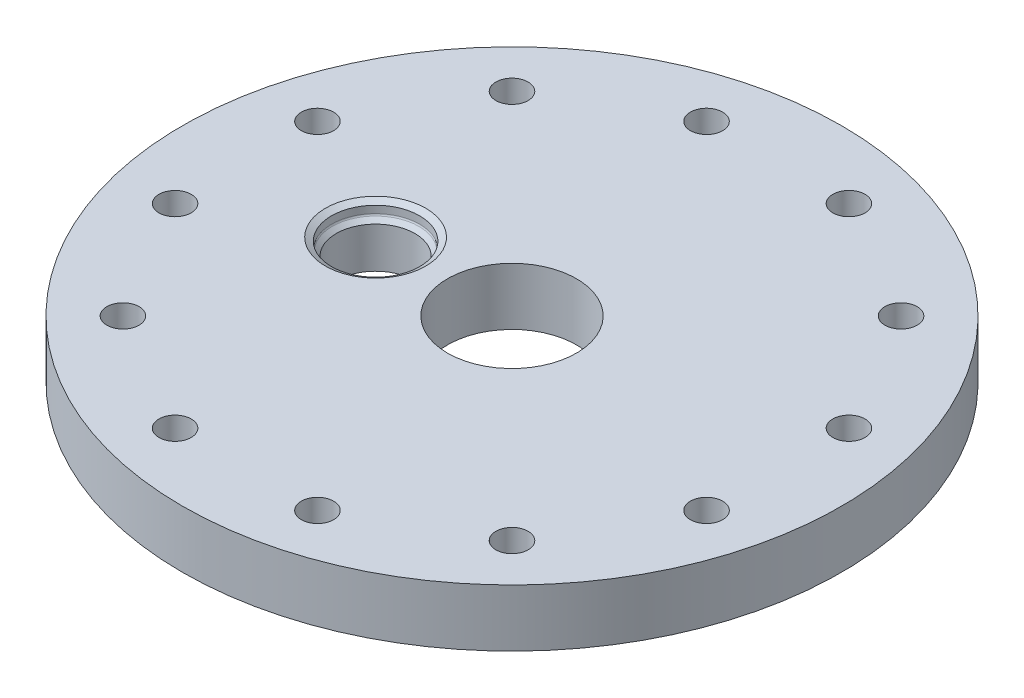
SolidWorks part; units mm, degrees
note: '?' marks a value the reader was unsure of.
material "7075-T6, Plate (SS)"
ref_plane "Front Plane" through (0, 0, 0) normal (0, 0, 1) x (1, 0, 0)
ref_plane "Top Plane" through (0, 0, 0) normal (0, 1, 0) x (1, 0, 0)
ref_plane "Right Plane" through (0, 0, 0) normal (1, 0, 0) x (0, 0, -1)
sketch "Top Plate Diameter" plane through (0, 0, 0) normal (0, 1, 0) x (1, 0, 0)
  circle A0 centre (0, 0) radius 73.025
  dimension "D1" = 146.05
extrude "Top Plate Extrude" add sketch "Top Plate Diameter" along normal blind 12.7
ref_axis "Center of Top Plate" through (0, 12.7, 0) along (0, -1, 0)?
sketch "Fuel Port Clearance Diameter" plane through (0, 12.7, 0) normal (0, 1, 0) x (1, 0, 0)
  circle A0 centre (0, 0) radius 14.2875
  dimension "D1" = 28.575
extrude "Fuel Port Clearance Hole" cut sketch "Fuel Port Clearance Diameter" against normal through all
hole_wizard "3/4-16 Tapped LOX Port" [suppressed] positions "3DSketch3" profile "Sketch6" tap size "3/4-16" standard "Ansi Inch"
sketch3d "3DSketch3"
  line L0 (0, 0, 0) -> (0, 37.9824, 0) construction
  point P0 (-30.226, 8.89, 0)
  dimension "D2" = 30.226
sketch "Sketch6" plane through (-30.226, 8.89, 0) normal (1, 0, 0) x (0, 0, 1)
  line L0 (0, 0) -> (0, 17.9463)
  line L1 (0, 17.9463) -> (8.7312, 12.7)
  line L2 (8.7312, 12.7) -> (8.7312, 0)
  line L5 (8.7312, 0) -> (0, 0)
  line L10 (0, 17.9463) -> (-8.7312, 12.7) construction
  line L11 (0, -6.35) -> (0, 107.95) construction
  dimension "Tap Drill Dia." = 17.4625
  dimension "Tap Drill Depth" = 12.7
  dimension "Drill Angle" = 118
cosmetic thread "Hole Thread2" [suppressed] parameters "D1"=38.1, "D2"=19.05
ref_plane "Assembly Bolt Offset Angle" through (0, 0, 0) normal (-0.2588, 0, 0.9659) x (0.9659, 0, 0.2588)
sketch "Assembly Bolt Diameter" plane through (0, 12.7, 0) normal (0, 1, 0) x (1, 0, 0)
  line L0 (-6.747, 1.8079) -> (6.747, -1.8079) construction
  circle A0 centre (-58.8828, 15.7776) radius 3.5719
  dimension "D1" = 7.1437
  dimension "D2" = 60.96
extrude "Assembly Bolt" cut sketch "Assembly Bolt Diameter" against normal up to next
pattern_circular "CirPattern1" count 12 over 360 about axis through (0, 0, 0) along (0, 1, 0) of "Assembly Bolt"
sketch "Sketch7" plane through (0, 12.7, 0) normal (0, 1, 0) x (1, 0, 0)
  line L0 (-6.985, 0) -> (6.985, 0) construction
  circle A0 centre (-30.226, 0) radius 8.7122
  dimension "D1" = 30.226
  dimension "D2" = 17.4244
extrude "LOX Port" cut sketch "Sketch7" against normal up to next
cosmetic thread "Cosmetic Thread1" parameters "D2"=19.05
cosmetic thread "Cosmetic Thread2" parameters "D2"=19.05
sketch "Sketch9" plane through (0, 0, 0) normal (0, 0, 1) x (1, 0, 0)
  line L0 (-30.226, 12.7) -> (-21.5138, 3.658) construction
  line L1 (-21.5138, 3.658) -> (-21.5138, 12.7) construction
  line L2 (-21.5138, 12.7) -> (-38.9382, 12.7) construction
  line L4 (-30.226, -7.4689) -> (-30.226, 31.4539) construction
  line L5 (-38.9382, 3.81) -> (-38.9382, 12.7) construction
  line L6 (-30.226, 12.7) -> (-38.9382, 3.81) construction
  line L7 (-41.3385, 12.7) -> (-39.9923, 11.9228)
  line L8 (-39.9923, 11.9228) -> (-39.9923, 10.3124)
  line L9 (-39.8435, 9.9532) -> (-38.9382, 9.0479)
  line L10 (-38.9382, 9.0479) -> (-38.9382, 12.7)
  line L11 (-38.9382, 12.7) -> (-41.3385, 12.7)
  line L12 (73.025, 12.7) -> (-73.025, 12.7) construction
  arc A0 (-39.8435, 9.9532) -> (-39.9923, 10.3124) centre (-39.4843, 10.3124) cw
  dimension "D4" = 0.508
  dimension "D1" = 45
  dimension "D2" = 11.1125
  dimension "D3" = 9.7663
  dimension "D5" = 2.3876
  dimension "D6" = 30
  dimension "D7" = 3.6521
  dimension "D8" = 2.4003
  dimension "D9" = 1.6104
  dimension "D10" = 0.9053
  dimension "D11" = 30.226
revolve "Cut-Revolve1" cut sketch "Sketch9" angle 360 about L4
thread "Thread1" [suppressed] pitch 1.5875 start angle 0, offset 0, length 0, pitch 1.5875, diameter 17.4244
ref_plane "Plane1" through (-37.2872, 9.0479, 0) normal (0, 0, 1) x (-1, 0, 0)
sketch "Thread Profile1" plane through (-37.2872, 9.0479, 0) normal (0, 0, 1) x (-1, 0, 0)
  line L0 (0, 0) -> (0, 1.5875) construction
  line L1 (0, 0) -> (0.8593, 0.4961)
  line L2 (0.8593, 0.4961) -> (0.8593, 0.6945)
  line L3 (0.8593, 0.6945) -> (0, 1.1906)
  line L4 (0.8593, 0.5953) -> (0, 0.5953) construction
  line L11 (0, 0) -> (0, 1.1906)
  point P2 (0, 0)
  dimension "Pitch" = 1.5875
  dimension "Profile_Angle" = 60
  dimension "Profile_Land" = 0.1984
  dimension "Profile_Height" = 0.8593
sketch "Sketch10" plane through (0, 0, 0) normal (0, 1, 0) x (1, 0, 0)
  circle A0 centre (0, 0) radius 52.4383
  circle A1 centre (0, 0) radius 49.8729
  dimension "D1" = 104.8766
  dimension "D2" = 99.7458
split line "Split Line1" [suppressed]
